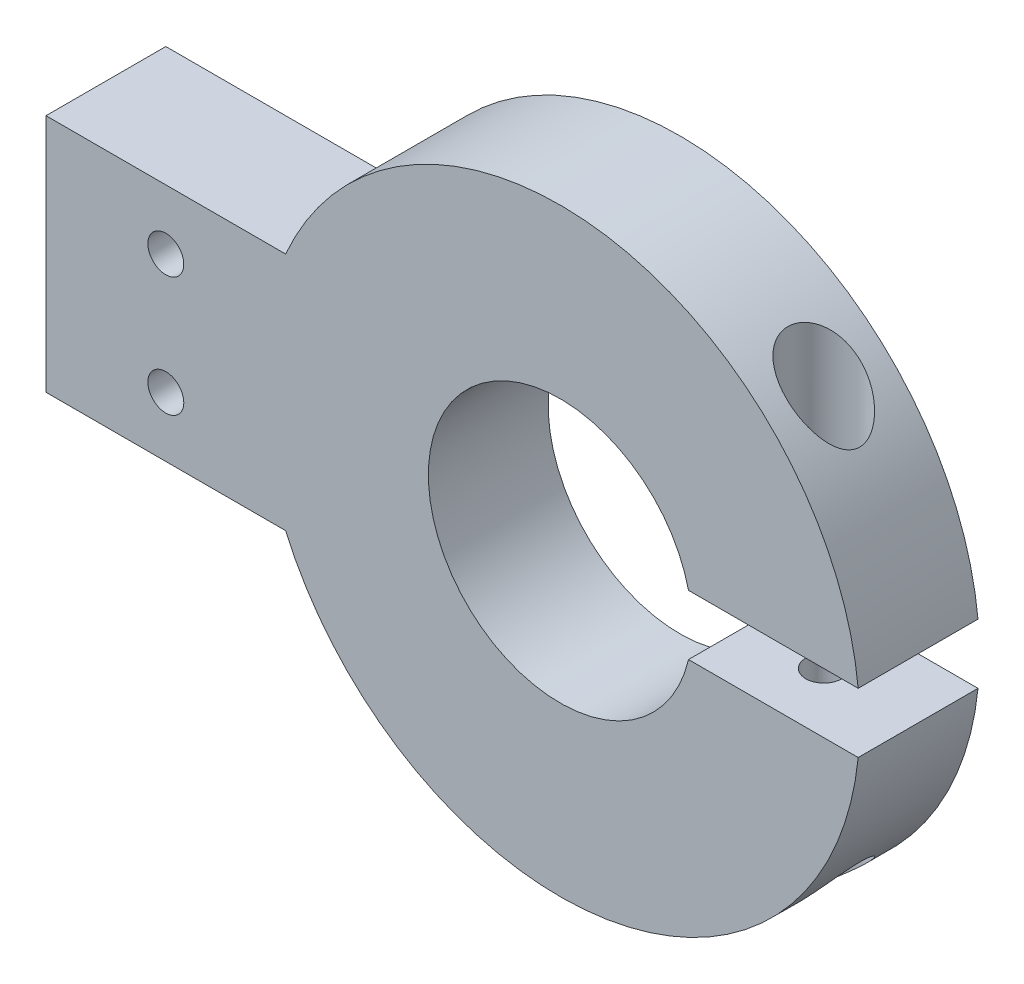
SolidWorks part; units mm, degrees
ref_plane "Front Plane" through (0, 0, 0) normal (0, 0, 1) x (1, 0, 0)
ref_plane "Top Plane" through (0, 0, 0) normal (0, 1, 0) x (1, 0, 0)
ref_plane "Right Plane" through (0, 0, 0) normal (1, 0, 0) x (0, 0, -1)
sketch "Sketch1" plane through (0, 0, 0) normal (0, 0, 1) x (1, 0, 0)
  circle A0 centre (0, 0) radius 11
  circle A1 centre (0, 0) radius 25
  dimension "D1" = 22
  dimension "D2" = 50
extrude "Boss-Extrude1" add sketch "Sketch1" along normal blind 10
sketch "Sketch2" plane through (0, 0, 10) normal (0, 0, 1) x (1, 0, 0)
  line L1 (25, 26.0035) -> (25, -24.7492) construction
  line L2 (25, 0) -> (25, 2.5)
  line L4 (0, 0) -> (0, -2.5)
  line L5 (0, -2.5) -> (25, -2.5)
  line L6 (25, 0) -> (25, -2.5)
  line L7 (25, 2.5) -> (0, 2.5)
  line L8 (0, 2.5) -> (0, 0)
  circle A0 centre (0, 0) radius 25 construction
  dimension "D1" = 2.5
  dimension "D2" = 2.5
extrude "Cut-Extrude1" cut sketch "Sketch2" against normal blind 10
sketch "Sketch5" plane through (0, -2.5, 0) normal (0, 1, 0) x (1, 0, 0)
  line L0 (10.7121, 0) -> (10.7121, -10) construction
  line L1 (10.7121, 0) -> (10.7121, -10) construction
  line L2 (24.8747, 0) -> (15.8747, 0) construction
  line L3 (24.8747, 0) -> (10.7121, 0) construction
  line L4 (17, -5) -> (13.0294, -5) construction
  circle A0 centre (17, -5) radius 1.5
  point P11 (22.8318, -4.8434)
  dimension "D2" = 3
  dimension "D1" = 9
extrude "Cut-Extrude4" cut sketch "Sketch5" against normal through all both and the other way through all
sketch "Sketch6" plane through (0, -2.5, 0) normal (0, 1, 0) x (1, 0, 0)
  line L0 (17, -5) -> (11.2324, -5) construction
  circle A1 centre (17, -5) radius 3
  point P1 (16.9915, -4.9527)
  dimension "D1" = 6
extrude "Cut-Extrude5" cut sketch "Sketch6" against normal blind 20 from offset 30
sketch "Sketch7" plane through (0, -2.5, 0) normal (0, 1, 0) x (1, 0, 0)
  line L0 (17, -5) -> (17.44, -5) construction
  line L3 (19.3094, -5) -> (18.1547, -3)
  line L4 (18.1547, -3) -> (15.8453, -3)
  line L5 (15.8453, -3) -> (14.6906, -5)
  line L6 (14.6906, -5) -> (15.8453, -7)
  line L7 (15.8453, -7) -> (18.1547, -7)
  line L8 (18.1547, -7) -> (19.3094, -5)
  circle A1 centre (17, -5) radius 2 construction
  point P0 (20.4838, -4.991)
  dimension "D1" = 4
extrude "Cut-Extrude6" cut sketch "Sketch7" along normal blind 25 from offset 30 offset against normal yes
sketch "Sketch8" plane through (0, -7.5, 0) normal (0, -1, 0) x (1, 0, 0)
  line L0 (17, 5) -> (8.6796, 5) construction
  circle A2 centre (17, 5) radius 3
  point P0 (17.2308, 4.9744)
  dimension "D1" = 6
extrude "Cut-Extrude8" cut sketch "Sketch8" against normal blind 15 from offset 20
sketch "Sketch9" plane through (0, 0, 0) normal (0, 0, -1) x (-1, 0, 0)
  line L0 (0, 0) -> (25, 0) construction
  line L1 (26.5121, 0) -> (26.5121, 9.9977) construction
  line L2 (26.5121, 9.9977) -> (22.9139, 9.9977) construction
  line L3 (22.9139, 9.9977) -> (22.9139, -9.9977)
  line L4 (22.9139, -9.9977) -> (42.9139, -9.9977)
  line L5 (42.9139, -9.9977) -> (42.9139, 9.9977)
  line L6 (42.9139, 9.9977) -> (22.9139, 9.9977)
  line L7 (22.9139, 9.9977) -> (42.9139, -9.9977) construction
  line L8 (42.9139, 9.9977) -> (22.9139, -9.9977) construction
  line L9 (32.9139, 9.9977) -> (32.9139, -9.9977) construction
  line L10 (32.9139, 0) -> (42.9139, 0) construction
  arc A0 (-24.8747, -2.5) -> (-24.8747, 2.5) centre (0, 0) ccw construction
  circle A1 centre (32.9139, 5) radius 1.5
  circle A2 centre (32.9139, -5) radius 1.5
  dimension "D2" = 3
  dimension "D1" = 20
extrude "Boss-Extrude2" add sketch "Sketch9" against normal blind 10
